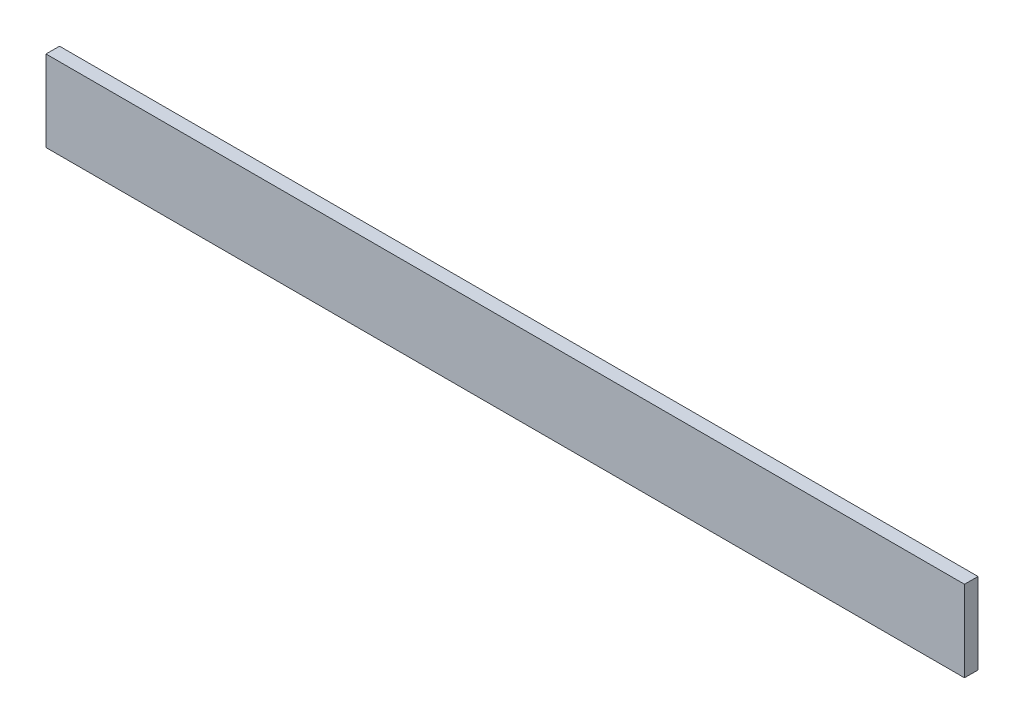
SolidWorks part; units mm, degrees
ref_plane "Front Plane" through (0, 0, 0) normal (0, 0, 1) x (1, 0, 0)
ref_plane "Top Plane" through (0, 0, 0) normal (0, 1, 0) x (1, 0, 0)
ref_plane "Right Plane" through (0, 0, 0) normal (1, 0, 0) x (0, 0, -1)
sketch "Sketch1" plane through (0, 0, 0) normal (0, 0, 1) x (1, 0, 0)
  line L1 (0, 0) -> (431.8, 0)
  line L2 (0, 0) -> (0, 38.1)
  line L3 (0, 38.1) -> (431.8, 38.1)
  line L4 (431.8, 0) -> (431.8, 38.1)
  dimension "D1" = 38.1
  dimension "D2" = 431.8
extrude "Boss-Extrude1" add sketch "Sketch1" along normal blind 6.35
sketch "Sketch3" plane through (0, 0, 6.35) normal (0, 0, 1) x (1, 0, 0)
  line L0 (9.525, 28.575) -> (204.3139, 9.525) construction
  line L1 (9.834, 31.7349) -> (204.623, 12.6849)
  line L2 (9.216, 25.4151) -> (204.0049, 6.3651)
  line L3 (9.525, 9.525) -> (204.3139, 28.575) construction
  line L4 (211.328, 38.1) -> (211.328, 0) construction
  line L7 (218.3421, 38.1) -> (218.3421, 0)
  line L8 (9.525, 28.575) -> (9.525, 9.525)
  line L9 (9.525, 9.525) -> (422.275, 9.525)
  line L10 (422.275, 9.525) -> (422.275, 28.575)
  line L11 (422.275, 28.575) -> (9.525, 28.575)
  line L12 (9.525, 28.575) -> (9.525, 9.525)
  line L13 (9.525, 9.525) -> (422.275, 9.525)
  line L15 (422.275, 28.575) -> (9.525, 28.575)
  line L16 (204.3139, 38.1) -> (204.3139, 0)
  line L17 (9.216, 12.6849) -> (204.0049, 31.7349)
  line L18 (9.834, 6.3651) -> (204.623, 25.4151)
  line L19 (215.9, 38.1) -> (215.9, 0) construction
  line L20 (211.328, 70.4248) -> (211.328, 0) construction
  line L21 (413.131, 9.525) -> (218.3421, 28.575) construction
  line L22 (413.44, 12.6849) -> (218.6511, 31.7349)
  line L23 (412.822, 6.3651) -> (218.033, 25.4151)
  line L24 (413.131, 28.575) -> (218.3421, 9.525) construction
  line L25 (412.822, 31.7349) -> (218.033, 12.6849)
  line L26 (413.44, 25.4151) -> (218.6511, 6.3651)
  line L27 (413.131, 37.592) -> (413.131, -0.508) construction
  line L28 (413.131, 37.592) -> (413.131, -0.508)
  arc A0 (218.3421, 38.1) -> (204.3139, 38.1) centre (211.328, 38.1) ccw
  arc A1 (204.3139, 0) -> (218.3421, 0) centre (211.328, 0) ccw
  arc A2 (9.834, 31.7349) -> (9.216, 25.4151) centre (9.525, 28.575) ccw
  arc A3 (204.0049, 6.3651) -> (204.623, 12.6849) centre (204.3139, 9.525) ccw
  arc A4 (9.216, 12.6849) -> (9.834, 6.3651) centre (9.525, 9.525) ccw
  arc A5 (204.623, 25.4151) -> (204.0049, 31.7349) centre (204.3139, 28.575) ccw
  arc A6 (413.44, 12.6849) -> (412.822, 6.3651) centre (413.131, 9.525) cw
  arc A7 (218.033, 25.4151) -> (218.6511, 31.7349) centre (218.3421, 28.575) cw
  arc A8 (412.822, 31.7349) -> (413.44, 25.4151) centre (413.131, 28.575) cw
  arc A9 (218.6511, 6.3651) -> (218.033, 12.6849) centre (218.3421, 9.525) cw
  point P7 (211.328, 19.05)
  point P16 (106.9195, 19.05)
  point P22 (106.9195, 19.05)
  point P33 (315.7365, 19.05)
  point P40 (315.7365, 19.05)
  dimension "D2" = 7.0141
  dimension "D3" = 3.175
  dimension "D1" = 9.525
extrude "Cut-Extrude1" [suppressed] cut sketch "Sketch3" against normal through all contours L12 L17 L2 | L1 L17 L15 | L18 L13 L2 | L18 L1 L16 | L25 L23 L7 | L25 L15 L22 | L23 L26 L13 | L28 L26 L22
fillet "Fillet1" [suppressed] radius 1.5875
move or copy body "Body-Move/Copy1" [suppressed] bodies to move or copy 101 parameters "D1"=0, "D2"=0, "D3"=0
